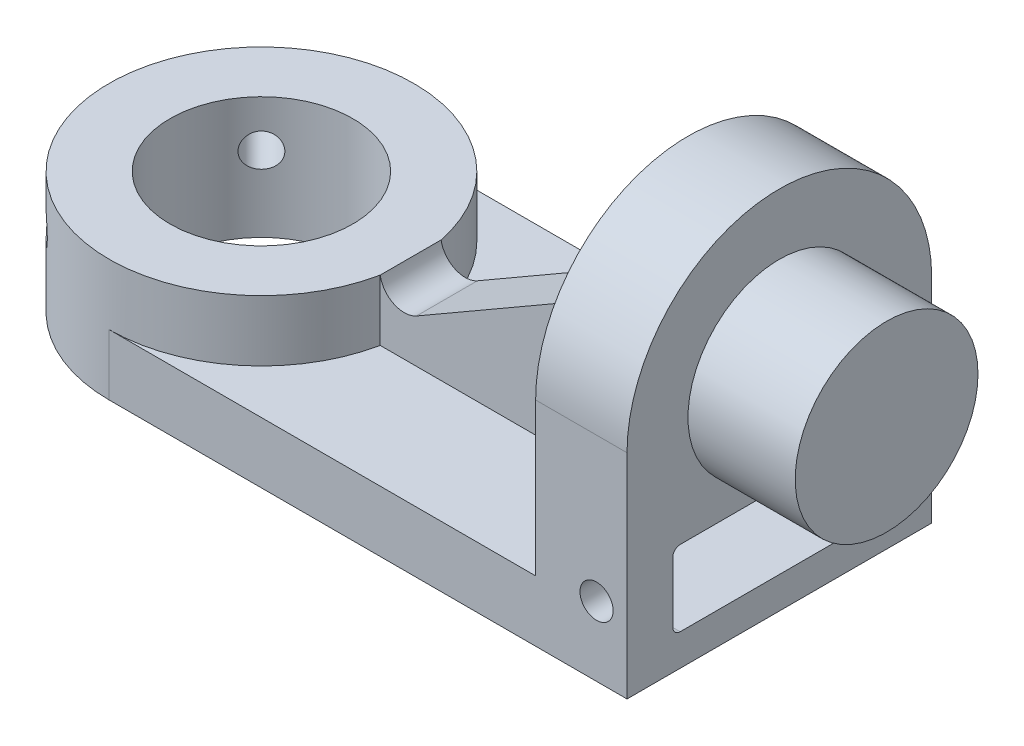
SolidWorks part; units mm, degrees
material "Alloy Steel"
ref_plane "Front Plane" through (0, 0, 0) normal (0, 0, 1) x (1, 0, 0)
ref_plane "Top Plane" through (0, 0, 0) normal (0, 1, 0) x (1, 0, 0)
ref_plane "Right Plane" through (0, 0, 0) normal (1, 0, 0) x (0, 0, -1)
sketch "Sketch1" plane through (0, 0, 0) normal (0, 1, 0) x (1, 0, 0)
  line L1 (0, 0) -> (53.975, 0)
  line L3 (0, 31.75) -> (53.975, 31.75)
  line L4 (53.975, 0) -> (53.975, 31.75)
  circle A0 centre (0, 15.875) radius 15.875
  circle A1 centre (0, 15.875) radius 9.525
  dimension "D3" = 19.05
  dimension "D1" = 31.75
  dimension "D2" = 53.975
extrude "Boss-Extrude1" add sketch "Sketch1" along normal blind 6.35 contours A0 L1 L4 L3 region at (33.0704, 0, -15.875)
extrude "Boss-Extrude2" add sketch "Sketch1<3>" along normal blind 12.7 contours A0 region at (-15.426, 0, -15.875)
sketch "Sketch1<3>" plane through (0, 0, 0) normal (0, 1, 0) x (1, 0, 0) same geometry as "Sketch1"
sketch "Sketch2" plane through (0, 6.35, 0) normal (0, 1, 0) x (1, 0, 0)
  line L0 (44.45, 19.05) -> (15.5543, 19.05)
  line L3 (15.5543, 12.7) -> (44.45, 12.7)
  line L5 (44.45, 31.75) -> (44.45, 19.05)
  line L6 (0, 31.75) -> (53.975, 31.75) construction
  line L7 (0, 0) -> (53.975, 0) construction
  line L8 (44.45, 0) -> (53.975, 0)
  line L9 (53.975, 0) -> (53.975, 31.75)
  line L10 (53.975, 31.75) -> (44.45, 31.75)
  line L11 (44.45, 12.7) -> (44.45, 0)
  circle A0 centre (0, 15.875) radius 15.875 construction
  arc A1 (15.5543, 19.05) -> (15.5543, 12.7) centre (0, 15.875) cw
  dimension "D3" = 15.875
  dimension "D1" = 9.525
  dimension "D2" = 6.35
  dimension "D4" = 12.7
extrude "Boss-Extrude3" add sketch "Sketch2" along normal blind 31.75
sketch "Sketch3" plane through (0, 0, -12.7) normal (0, 0, 1) x (1, 0, 0)
  line L0 (15.5543, 12.7) -> (15.5543, 38.1)
  line L1 (15.5543, 38.1) -> (44.45, 38.1)
  line L2 (44.45, 38.1) -> (44.45, 6.35) construction
  line L3 (44.45, 25.4) -> (44.45, 6.35)
  line L4 (44.45, 38.1) -> (44.45, 6.35) construction
  line L5 (44.45, 6.35) -> (15.5543, 6.35)
  line L6 (44.45, 25.4) -> (19.3328, 10.8986)
  line L7 (44.45, 38.1) -> (44.45, 25.4)
  circle A0 centre (18.0628, 13.0983) radius 2.54 construction
  arc A1 (15.5543, 12.7) -> (19.3328, 10.8986) centre (18.0628, 13.0983) ccw
  line M6 (44.45, 6.35) -> (44.45, 38.1)
  line M7 (44.45, 38.1) -> (15.5543, 38.1)
  line M8 (15.5543, 38.1) -> (15.5543, 12.7)
  dimension "D3" = 5.08
  dimension "D1" = 30
  dimension "D2" = 19.05
extrude "Cut-Extrude1" cut sketch "Sketch3" against normal up to next contours A1 L6 M8 M6 M7 region at (28.1754, 27.1469, -12.7)
sketch "Sketch4" plane through (53.975, 0, 0) normal (1, 0, 0) x (0, 0, -1)
  line L0 (0, 38.1) -> (0, 0) construction
  line L1 (31.75, 38.1) -> (31.75, 0) construction
  line L2 (0, 38.1) -> (31.75, 38.1) construction
  line L3 (0, 22.225) -> (-5.8106, 22.225)
  line L4 (-5.8106, 22.225) -> (-5.8106, 42.5587)
  line L5 (-5.8106, 42.5587) -> (36.0757, 42.5587)
  line L6 (36.0757, 42.5587) -> (36.0757, 22.225)
  line L7 (36.0757, 22.225) -> (31.75, 22.225)
  line L8 (4.7752, 10.414) -> (4.7752, 4.064)
  line L9 (26.9748, 4.064) -> (26.9748, 10.414)
  line L10 (26.2128, 11.176) -> (5.5372, 11.176)
  line L11 (5.5372, 3.302) -> (26.2128, 3.302)
  circle A0 centre (15.875, 22.225) radius 9.525
  arc A1 (0, 22.225) -> (31.75, 22.225) centre (15.875, 22.225) cw
  arc A2 (26.9748, 10.414) -> (26.2128, 11.176) centre (26.2128, 10.414) ccw
  arc A3 (26.9748, 4.064) -> (26.2128, 3.302) centre (26.2128, 4.064) cw
  arc A4 (4.7752, 4.064) -> (5.5372, 3.302) centre (5.5372, 4.064) ccw
  arc A5 (5.5372, 11.176) -> (4.7752, 10.414) centre (5.5372, 10.414) ccw
  line M6 (31.75, 0) -> (31.75, 38.1)
  line M7 (31.75, 38.1) -> (0, 38.1)
  line M8 (0, 38.1) -> (0, 0)
  dimension "D1" = 19.05
  dimension "D6" = 0.762
  dimension "D7" = 0.762
  dimension "D8" = 0.762
  dimension "D9" = 0.762
  dimension "D2" = 4.7752
  dimension "D3" = 4.7752
  dimension "D4" = 7.874
  dimension "D5" = 11.049
extrude "Boss-Extrude4" add sketch "Sketch4" along normal blind 11.176 separate body contours A0 region at (53.975, 22.225, -15.875)
extrude "Cut-Extrude5" cut sketch "Sketch4<3>" along direction (1, 0, 0) on the side against the normal blind 11.176 contours L7 L6 L5 L4 L3 M8 M7 M6 | A1 M8 M7 | A1 M7 M6 region at (53.975, 34.554, -3.546) region at (53.975, 22.6906, 2.9053) region at (53.975, 34.554, -28.204)
sketch "Sketch4<3>" plane through (53.975, 0, 0) normal (1, 0, 0) x (0, 0, -1) same geometry as "Sketch4"
extrude "Cut-Extrude6" cut sketch "Sketch4<4>" against normal blind 8.001 contours L10 A5 L8 A4 L11 A3 L9 A2 region at (53.975, 7.239, -15.875)
sketch "Sketch4<4>" plane through (53.975, 0, 0) normal (1, 0, 0) x (0, 0, -1) same geometry as "Sketch4"
sketch "Sketch5" plane through (0, 12.7, 0) normal (0, 1, 0) x (1, 0, 0)
  line L0 (0, 15.875) -> (-11.2253, 27.1003) construction
  line L1 (0, 15.875) -> (0, 31.75) construction
  line L2 (0, 15.875) -> (-15.875, 15.875) construction
  line L3 (0, 15.875) -> (-11.2253, 4.6497) construction
  circle A0 centre (0, 15.875) radius 15.875
  dimension "D1" = 31.75
  dimension "D2" = 45
  dimension "D3" = 45
ref_plane "Plane1" through (-19.1628, 0, -19.1628) normal (-0.7071, 0, -0.7071) x (-0.7071, 0, 0.7071)
sketch "Sketch6" plane through (-19.1628, 0, -19.1628) normal (-0.7071, 0, -0.7071) x (-0.7071, 0, 0.7071)
  line L0 (4.6497, 12.7) -> (-27.1003, 12.7) construction
  circle A0 centre (-11.2253, 7.874) radius 1.7272
  dimension "D1" = 3.4544
  dimension "D2" = 4.826
extrude "Cut-Extrude7" cut sketch "Sketch6" against normal blind 8.001
ref_plane "Plane2" through (-11.2253, 12.7, -4.6497) normal (-0.7071, 0, 0.7071) x (0.7071, 0, 0.7071)
sketch "Sketch7" plane through (-11.2253, 12.7, -4.6497) normal (-0.7071, 0, 0.7071) x (0.7071, 0, 0.7071)
  line L0 (15.875, 0) -> (-15.875, 0) construction
  circle A0 centre (0, -4.826) radius 1.7272
  dimension "D2" = 3.4544
  dimension "D1" = 4.826
extrude "Cut-Extrude8" cut sketch "Sketch7" against normal blind 8.001
sketch "Sketch8" plane through (0, 0, 0) normal (0, 0, 1) x (1, 0, 0)
  line L0 (53.975, 22.225) -> (53.975, 0) construction
  line L1 (0, 0) -> (53.975, 0) construction
  circle A0 centre (50.8, 7.239) radius 1.7272
  dimension "D1" = 3.4544
  dimension "D2" = 3.175
  dimension "D3" = 7.239
extrude "Cut-Extrude9" cut sketch "Sketch8" against normal blind 32.131
